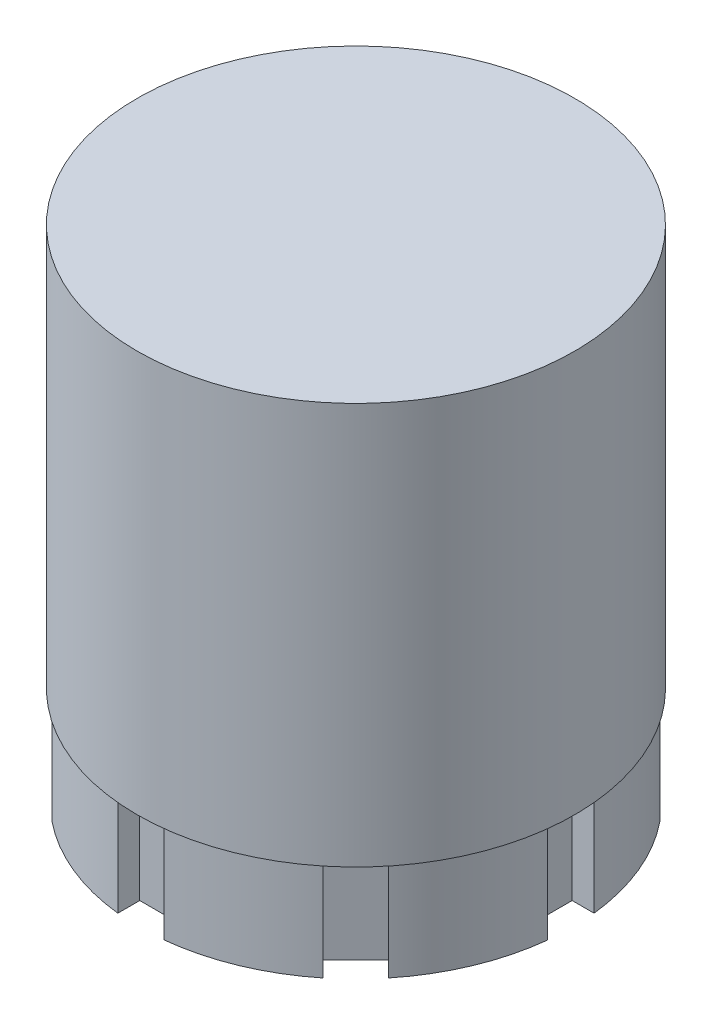
SolidWorks part; units mm, degrees
ref_plane "Front Plane" through (0, 0, 0) normal (0, 0, 1) x (1, 0, 0)
ref_plane "Top Plane" through (0, 0, 0) normal (0, 1, 0) x (1, 0, 0)
ref_plane "Right Plane" through (0, 0, 0) normal (1, 0, 0) x (0, 0, -1)
ref_axis "Axis1" through (0, 21.59, 0) along (0, -1, 0)
sketch "Sketch1" plane through (0, 0, 0) normal (0, 1, 0) x (1, 0, 0)
  circle A0 centre (0, 0) radius 22.5
  dimension "D1" = 45
extrude "Boss-Extrude1" add sketch "Sketch1" along normal mid plane 41.275
sketch "Sketch3" plane through (0, -20.6375, 0) normal (0, -1, 0) x (-1, 0, 0)
  circle A0 centre (0, 0) radius 22.225
  dimension "D1" = 44.45
extrude "Boss-Extrude2" add sketch "Sketch3" along normal blind 10.16
sketch "Sketch4" plane through (0, -30.7975, 0) normal (0, -1, 0) x (1, 0, 0)
  line L1 (-2.3812, 19.8437) -> (2.3812, 19.8437)
  line L2 (-2.3812, 19.8437) -> (-2.3812, 24.6062)
  line L3 (-2.3812, 24.6062) -> (2.3812, 24.6062)
  line L4 (2.3812, 19.8437) -> (2.3812, 24.6062)
  line L5 (-2.3812, 19.8437) -> (2.3812, 24.6062) construction
  line L6 (-2.3812, 24.6062) -> (2.3812, 19.8437) construction
  circle A0 centre (0, 0) radius 22.225 construction
  point P0 (0, 22.225)
  dimension "D1" = 4.7625
extrude "Cut-Extrude2" cut sketch "Sketch4" against normal up to surface (10.16 mm away) up to face at (0, -20.6375, -22.225)
pattern_circular "CirPattern2" count 8 over 360 about axis through (0, 21.59, 0) along (0, -1, 0) of "Cut-Extrude2"
